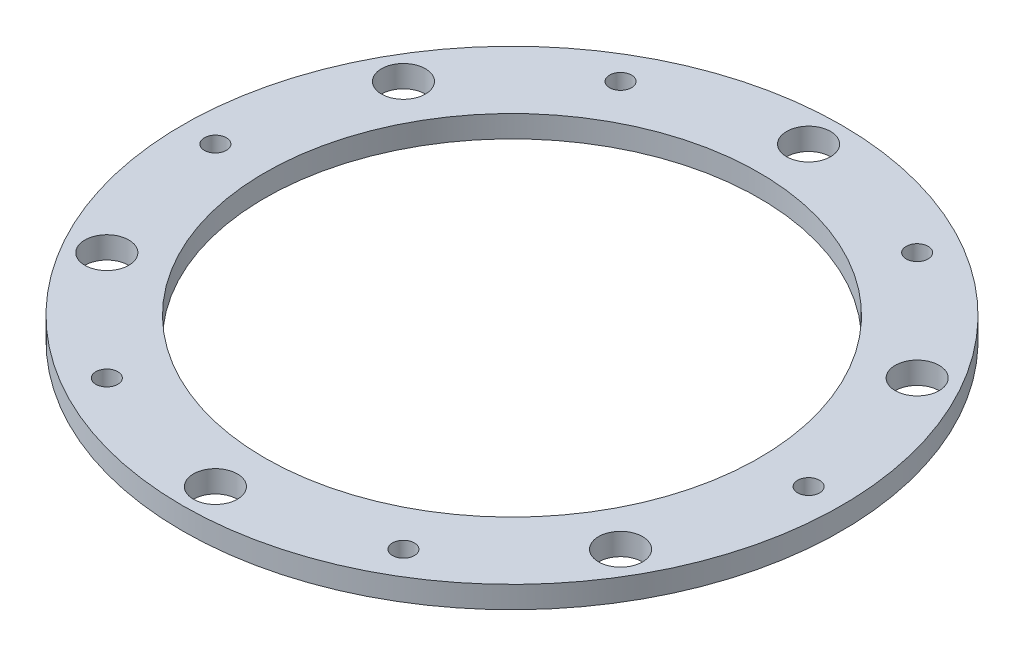
SolidWorks part; units mm, degrees
ref_plane "Front Plane" through (0, 0, 0) normal (0, 0, 1) x (1, 0, 0)
ref_plane "Top Plane" through (0, 0, 0) normal (0, 1, 0) x (1, 0, 0)
ref_plane "Right Plane" through (0, 0, 0) normal (1, 0, 0) x (0, 0, -1)
sketch "Sketch1" plane through (0, 0, 0) normal (0, 1, 0) x (1, 0, 0)
  circle A0 centre (0, 0) radius 30
  circle A1 centre (0, 0) radius 27 construction
  circle A2 centre (0, 27) radius 2
  circle A3 centre (23.3827, 13.5) radius 2
  circle A4 centre (23.3827, -13.5) radius 2
  circle A5 centre (0, -27) radius 2
  circle A6 centre (-23.3827, -13.5) radius 2
  circle A7 centre (-23.3827, 13.5) radius 2
  circle A8 centre (0, 0) radius 22.5
  point P18 (0, 0)
  dimension "D1" = 60
  dimension "D2" = 54
  dimension "D3" = 4
  dimension "D5" = 45
  dimension "D4" = 6
extrude "Boss-Extrude1" add sketch "Sketch1" along normal blind 2
sketch "Sketch3" plane through (0, 2, 0) normal (0, 1, 0) x (1, 0, 0)
  line L0 (-13.5, 23.3827) -> (0, 0) construction
  line L1 (0, 0) -> (12.944, 0) construction
  circle A0 centre (0, 0) radius 27 construction
  circle A1 centre (-13.5, 23.3827) radius 1
  circle A2 centre (13.5, 23.3827) radius 1
  circle A3 centre (27, 0) radius 1
  circle A4 centre (13.5, -23.3827) radius 1
  circle A5 centre (-13.5, -23.3827) radius 1
  circle A6 centre (-27, 0) radius 1
  point P17 (0, 0)
  dimension "D1" = 54
  dimension "D2" = 2
  dimension "D4" = 120
  dimension "D3" = 6
extrude "Cut-Extrude1" cut sketch "Sketch3" against normal blind 3
